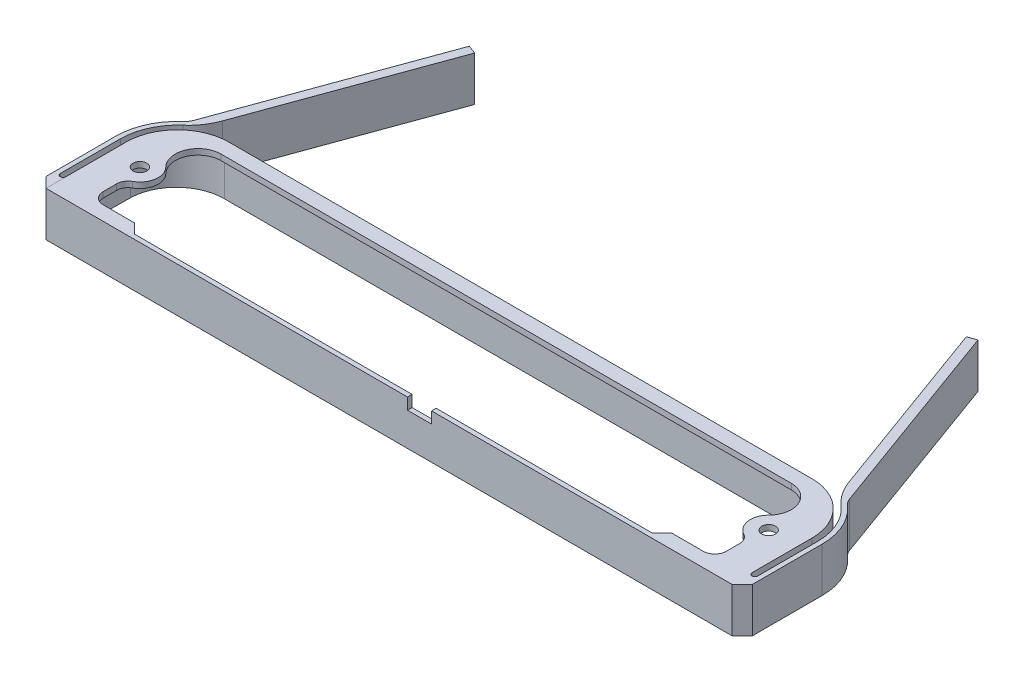
SolidWorks part; units mm, degrees
material "ABS"
ref_plane "Front" through (0, 0, 0) normal (0, 0, 1) x (1, 0, 0)
ref_plane "Top" through (0, 0, 0) normal (0, 1, 0) x (1, 0, 0)
ref_plane "Right" through (0, 0, 0) normal (1, 0, 0) x (0, 0, -1)
ref_axis "X" through (-80.9, 0, 0) along (1, 0, 0)
ref_axis "Y" through (0, -50, 0) along (0, 1, 0)
ref_axis "Z" through (0, 0, -80.9) along (0, 0, 1)
sketch "Sketch1" plane through (0, 0, 0) normal (0, 1, 0) x (1, 0, 0)
  line L0 (-60, 0) -> (-54.5, 0)
  line L2 (-49.8878, 20.5) -> (49.8878, 20.5)
  line L4 (54.5, 0) -> (60, 0)
  line L5 (60, 0) -> (60, 14)
  line L6 (51, 23) -> (-51, 23)
  line L7 (-60, 14) -> (-60, 0)
  line L8 (-54.5, 0) -> (54.5, 0)
  line L9 (-47, 0.8) -> (47, 0.8)
  line L10 (-54.5, 0) -> (-54.5, 0.8) construction
  line L11 (54.5, 0) -> (54.5, 0.8) construction
  line L12 (55, 11.43) -> (-55, 11.43) construction
  line L13 (0, 11.43) -> (0, 0) construction
  line L14 (54.5, 2.5) -> (47, 2.5)
  line L15 (47, 2.5) -> (47, 0.8)
  line L16 (-54.5, 2.5) -> (-47, 2.5)
  line L17 (-47, 2.5) -> (-47, 0.8)
  line L18 (-54.5, 0.8) -> (-54.5, 2.5) construction
  line L19 (-54.5, 0.8) -> (-47, 0.8) construction
  line L20 (54.5, 2.5) -> (54.5, 0.8) construction
  line L21 (47, 0.8) -> (54.5, 0.8) construction
  line L22 (54.5, 8.2693) -> (54.5, 2.5)
  line L23 (-54.5, 2.5) -> (-54.5, 8.2693)
  arc A0 (-52.7279, 13.6833) -> (-49.8878, 20.5) centre (-49.8878, 16.5) cw
  arc A1 (49.8878, 20.5) -> (52.7279, 13.6833) centre (49.8878, 16.5) cw
  arc A2 (60, 14) -> (51, 23) centre (51, 14) ccw
  arc A3 (-51, 23) -> (-60, 14) centre (-51, 14) ccw
  circle A4 centre (55, 11.43) radius 1.2
  circle A5 centre (-55, 11.43) radius 1.2
  arc A6 (52.7279, 13.6833) -> (54.5, 8.2693) centre (55, 11.43) ccw
  arc A7 (-52.7279, 13.6833) -> (-54.5, 8.2693) centre (-55, 11.43) cw
  dimension "D5" = 9
  dimension "D6" = 4
  dimension "D10" = 2.4
  dimension "D13" = 3.2
  dimension "D1" = 120
  dimension "D2" = 5.5
  dimension "D3" = 2.5
  dimension "D4" = 23
  dimension "D7" = 0.8
  dimension "D8" = 11.43
  dimension "D9" = 110
  dimension "D11" = 13
  dimension "D12" = 2.5
extrude "Boss-Extrude1" add sketch "Sketch1" along normal blind 1
sketch "Sketch8" plane through (0, 0, 0) normal (0, -1, 0) x (-1, 0, 0)
  line L0 (-59.2, 0.8) -> (59.2, 0.8)
  line L1 (59.2, 0.8) -> (59.2, 14)
  line L2 (51, 22.2) -> (-51, 22.2)
  line L3 (-59.2, 14) -> (-59.2, 0.8)
  line L4 (60, 0) -> (60, 14)
  line L5 (51, 23) -> (-51, 23)
  line L6 (-60, 14) -> (-60, 0)
  line L7 (-60, 0) -> (60, 0)
  line L8 (60, 0) -> (60, 14)
  line L9 (51, 23) -> (-51, 23)
  line L10 (-60, 14) -> (-60, 0)
  line L11 (-60, 0) -> (60, 0)
  arc A0 (59.2, 14) -> (51, 22.2) centre (51, 14) ccw
  arc A1 (-51, 22.2) -> (-59.2, 14) centre (-51, 14) ccw
  arc A2 (60, 14) -> (51, 23) centre (51, 14) ccw
  arc A3 (-51, 23) -> (-60, 14) centre (-51, 14) ccw
  arc A4 (60, 14) -> (51, 23) centre (51, 14) ccw
  arc A5 (-51, 23) -> (-60, 14) centre (-51, 14) ccw
  dimension "D1" = 0
  dimension "D2" = 0.8
extrude "Boss-Extrude2" add sketch "Sketch8" along normal blind 8.2 from surface starting at face at (55, 1, -10.23)
chamfer "Chamfer1" distance 1 angle 45 7 edges at (59.2, 0, -7.4) (56.7983, 0, -19.7983) (-59.2, 0, -7.4) (-56.7983, 0, -19.7983) (53.1, 0, -0.8) (-53.1, 0, -0.8) (0, 0, -22.2)
sketch "Sketch9" plane through (0, 0, 0) normal (1, 0, 0) x (0, 0, -1)
  line L0 (-2, -7.2) -> (23, -7.2)
  line L1 (23, -7.2) -> (-2, -6.7636)
  line L3 (-2, -6.7636) -> (-2, -7.2)
  dimension "D1" = 25
  dimension "D2" = 1
extrude "Cut-Extrude1" cut sketch "Sketch9" against normal through all both and the other way through all
sketch "Sketch11" plane through (0, 0, 0) normal (0, 0, 1) x (1, 0, 0)
  line L0 (3.25, 1) -> (3.25, -1)
  line L1 (-60, 1) -> (60, 1) construction
  line L2 (3.25, -1) -> (7.45, -1)
  line L3 (7.45, -1) -> (7.45, 1)
  line L4 (7.45, 1) -> (3.25, 1)
  line L5 (5.35, -1) -> (5.35, 1) construction
  line L7 (60, 1) -> (60, -6.7985) construction
  dimension "D1" = 54.65
  dimension "D2" = 4.2
  dimension "D3" = 2
extrude "Cut-Extrude2" cut sketch "Sketch11" against normal up to next
fillet "Fillet1" radius 2 4 edges at (-54.5, 0.5, -8.2693) (-54.5, 0.5, -2.5) (54.5, 0.5, -2.5) (54.5, 0.5, -8.2693)
chamfer "Chamfer2" distance 1.7 angle 45 2 edges at (-47, 0, -0.8) (47, 0, -0.8)
sketch "Sketch12" plane through (0, 0, 0) normal (0, 1, 0) x (1, 0, 0)
  line L0 (-50.876, 24) -> (-50.876, 24.8) construction
  line L1 (-60, 0) -> (60, 0) construction
  line L3 (-70.0161, 72.0463) -> (123.9526, 72.0463) construction
  line L9 (-60, 0) -> (-61.8, 1.8)
  line L10 (7.45, 0) -> (60, 0) construction
  line L11 (0, 38.0905) -> (0, 0) construction
  line L21 (-46.1776, 27.2899) -> (-35, 58)
  line L22 (-35, 58) -> (-36.5035, 58.5472)
  line L23 (-36.5035, 58.5472) -> (-48.0718, 26.7635)
  line L27 (51, 23) -> (-51, 23) construction
  line L31 (-60, 0) -> (-60, 3.5)
  line L32 (-60, 14) -> (-60, 0) construction
  line L34 (-61.8, 1.8) -> (-61.8, 14)
  line L35 (-51, 24.8) -> (-50.876, 24.8)
  line L36 (-61, 3.5) -> (-61, 14)
  line L37 (-51, 24) -> (-50.876, 24)
  line L39 (-51, 24) -> (-51, 24.8) construction
  line L40 (-61, 14) -> (-61.8, 14) construction
  arc A3 (-61.8, 14) -> (-51, 24.8) centre (-51, 14) cw
  arc A4 (-61, 14) -> (-51, 24) centre (-51, 14) cw
  arc A5 (-61, 3.5) -> (-60, 3.5) centre (-60.5, 3.5) ccw
  arc A7 (-51, 23) -> (-60, 14) centre (-51, 14) ccw construction
  arc A8 (-50.876, 24) -> (-46.1776, 27.2899) centre (-50.876, 29) ccw
  arc A9 (-50.876, 24.8) -> (-48.0718, 26.7635) centre (-50.876, 27.7842) ccw
  dimension "D7" = 5
  dimension "D3" = 72.0463
  dimension "D9" = 20
  dimension "D11" = 35
  dimension "D12" = 1.6
  dimension "D14" = 35
  dimension "D2" = 45
  dimension "D4" = 1
  dimension "D5" = 0.8
  dimension "D6" = 3.5
extrude "Boss-Extrude3" [suppressed] add sketch "Sketch12" against normal blind 7 from surface starting at face at (0.8231, 1, -7.7026)
mirror "Mirror2" [suppressed] about plane through (0, 0, 0) normal (1, 0, 0)
sketch "Sketch14" plane through (0, 0, 0) normal (0, 1, 0) x (1, 0, 0)
  line L0 (-57.591, 21.5206) -> (-58.1182, 22.1222) construction
  line L1 (-60, 14) -> (-60, 0) construction
  line L2 (7.45, 0) -> (60, 0) construction
  line L3 (-70.0161, 72.0463) -> (123.9526, 72.0463) construction
  line L9 (-60, 0) -> (-61.8, 1.8)
  line L10 (51, 23) -> (-51, 23) construction
  line L11 (0, 38.0905) -> (0, 0) construction
  line L21 (-54.785, 25.621) -> (-43, 58)
  line L22 (-43, 58) -> (-44.5035, 58.5472)
  line L23 (-44.5035, 58.5472) -> (-57.3554, 23.237)
  line L31 (-60, 0) -> (-60, 3.5)
  line L34 (-61.8, 1.8) -> (-61.8, 14)
  line L36 (-61, 3.5) -> (-61, 14)
  line L40 (-61, 14) -> (-61.8, 14) construction
  arc A3 (-61.8, 14) -> (-58.1182, 22.1222) centre (-51, 14) cw
  arc A4 (-61, 14) -> (-57.591, 21.5206) centre (-51, 14) cw
  arc A5 (-61, 3.5) -> (-60, 3.5) centre (-60.5, 3.5) ccw
  arc A6 (-51, 23) -> (-60, 14) centre (-51, 14) ccw construction
  arc A8 (-57.591, 21.5206) -> (-54.785, 25.621) centre (-64.1819, 29.0412) ccw
  arc A9 (-58.1182, 22.1222) -> (-57.3554, 23.237) centre (-59.9102, 24.1669) ccw
  point P2 (0, 0)
  point P3 (-60, 4.0053)
  point P10 (0, 0)
  point P15 (0, 0)
  point P19 (0, 0)
  point P24 (0, 0)
  point P32 (-50.8752, 24)
  point P33 (-50.5437, 24.7904)
  point P34 (-48.4444, 24)
  point P39 (0, 0)
  point P41 (0, 0)
  dimension "D7" = 10
  dimension "D8" = 35
  dimension "D4" = 1
  dimension "D2" = 45
  dimension "D3" = 72.0463
  dimension "D5" = 0.8
  dimension "D6" = 3.5
  dimension "D9" = 20
  dimension "D12" = 1.6
  dimension "D14" = 43
extrude "Boss-Extrude4" add sketch "Sketch14" against normal blind 7.7985 from surface separate body starting at face at (0.8231, 1, -7.7026)
mirror "Mirror5" about plane through (0, 0, 0) normal (1, 0, 0) of "Boss-Extrude4"
equation "\"D3@Sketch12\"=200-127.95373"
